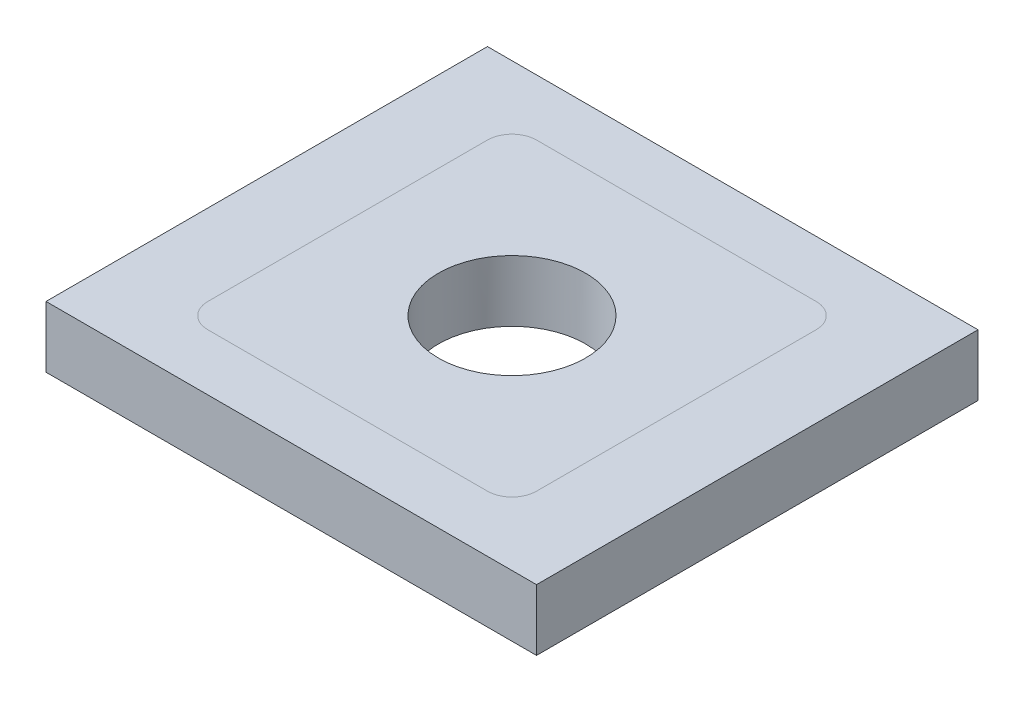
SolidWorks part; units mm, degrees
material "6061-T4 (SS)"
ref_plane "Front Plane" through (0, 0, 0) normal (0, 0, 1) x (1, 0, 0)
ref_plane "Top Plane" through (0, 0, 0) normal (0, 1, 0) x (1, 0, 0)
ref_plane "Right Plane" through (0, 0, 0) normal (1, 0, 0) x (0, 0, -1)
sketch "Sketch1" plane through (0, 0, 0) normal (0, 1, 0) x (1, 0, 0)
  line L1 (100, 90) -> (-100, 90)
  line L2 (100, 90) -> (100, -90)
  line L3 (100, -90) -> (-100, -90)
  line L4 (-100, 90) -> (-100, -90)
  line L5 (100, 90) -> (-100, -90) construction
  line L6 (100, -90) -> (-100, 90) construction
  point P0 (0, 0)
  dimension "D1" = 200
  dimension "D2" = 180
extrude "base" add sketch "Sketch1" along normal blind 25 contours L1 L4 L3 L2
sketch "Sketch2" plane through (0, 25, 0) normal (0, 1, 0) x (1, 0, 0)
  circle A0 centre (0, 0) radius 30
  dimension "D1" = 60
extrude "actuator cut" cut sketch "Sketch2" against normal blind 40
sketch "Sketch3" plane through (0, 25, 0) normal (0, 1, 0) x (1, 0, 0)
  line L1 (57, 67) -> (-57, 67)
  line L2 (67, 57) -> (67, -57)
  line L3 (57, -67) -> (-57, -67)
  line L4 (-67, 57) -> (-67, -57)
  line L5 (67, 67) -> (-67, -67) construction
  line L6 (67, -67) -> (-67, 67) construction
  arc A0 (-57, -67) -> (-67, -57) centre (-57, -57) cw
  arc A1 (67, -57) -> (57, -67) centre (57, -57) cw
  arc A2 (57, 67) -> (67, 57) centre (57, 57) cw
  arc A3 (-57, 67) -> (-67, 57) centre (-57, 57) ccw
  point P0 (0, 0)
  dimension "D2" = 10
  dimension "D3" = 134
  dimension "D4" = 134
split line "Split Line1"
